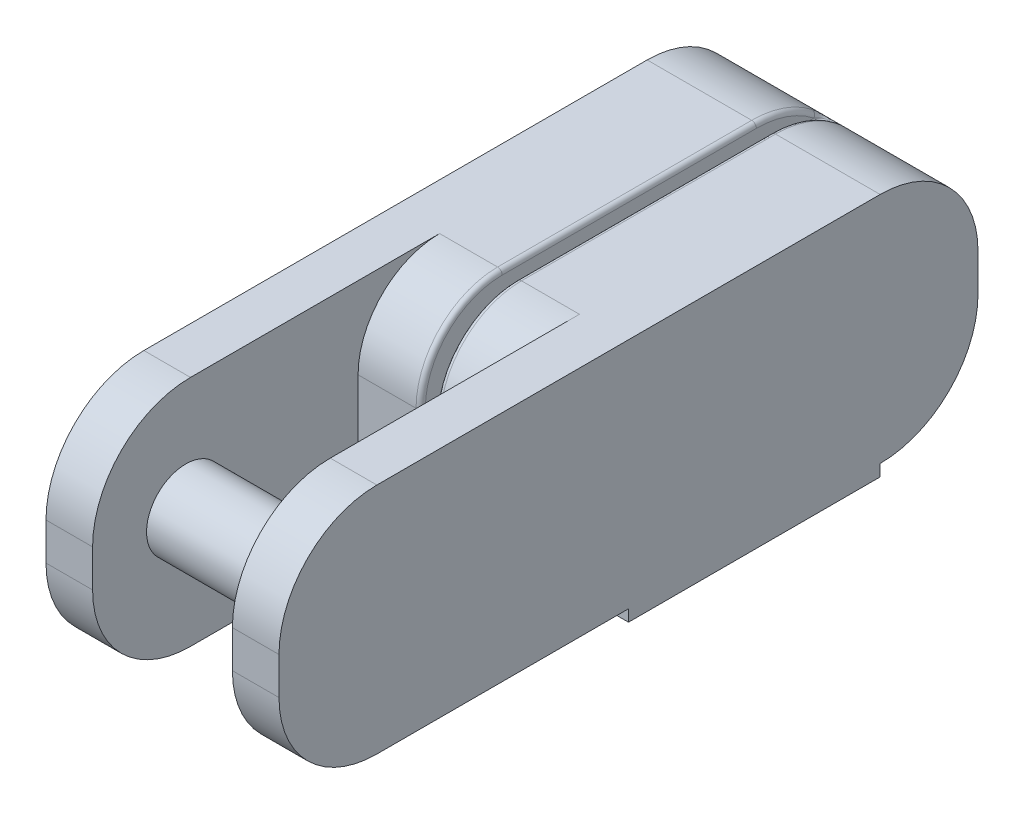
SolidWorks part; units mm, degrees
ref_plane "Front Plane" through (0, 0, 0) normal (0, 0, 1) x (1, 0, 0)
ref_plane "Top Plane" through (0, 0, 0) normal (0, 1, 0) x (1, 0, 0)
ref_plane "Right Plane" through (0, 0, 0) normal (1, 0, 0) x (0, 0, -1)
sketch "Sketch2" plane through (0, 0, 0) normal (0, 1, 0) x (1, 0, 0)
  line L0 (-31.2782, 19.6442) -> (-18.5782, 19.6442)
  line L2 (-31.2782, 19.6442) -> (-31.2782, -18.4558)
  line L3 (-31.2782, -18.4558) -> (-28.7382, -18.4558)
  line L4 (-18.5782, 19.6442) -> (-18.5782, -18.4558)
  line L7 (-28.7382, -18.4558) -> (-28.7382, -3.9858)
  line L8 (-28.7382, -3.9858) -> (-21.1182, -3.9858)
  line L9 (-21.1182, -3.9858) -> (-21.1182, -18.4558)
  line L10 (-31.2782, -3.9858) -> (-18.5782, -3.9858)
  line L11 (-21.1182, -18.4558) -> (-18.5782, -18.4558)
  point P3 (-30.0082, -18.4558)
  dimension "D1" = 38.1
  dimension "D2" = 12.7
  dimension "D3" = 2.54
  dimension "D4" = 2.54
  dimension "D8" = 14.47
extrude "Boss-Extrude1" add sketch "Sketch2" along normal blind 12.7 contours L2 L10 L8 L4 L0 | L0 | L9 L11 L4 L10 | L10 L2 L3 L7 region at (-24.9282, 0, -7.8292) region at (-30.0082, 0, 11.2208) region at (-19.8482, 0, 11.2208)
sketch "Sketch3" plane through (0, 0, 0) normal (1, 0, 0) x (0, 0, -1)
  line L0 (-13.3758, 12.7) -> (-13.3758, 0) construction
  line L1 (19.6442, 12.7) -> (-18.4558, 12.7) construction
  line L2 (19.6442, 0) -> (-18.4558, 0) construction
  line L3 (-18.4558, 12.7) -> (-18.4558, 0) construction
  line L4 (-18.4558, 6.6407) -> (19.6442, 6.35) construction
  line L6 (19.6442, 12.7) -> (19.6442, 0) construction
  circle A2 centre (-13.3758, 6.6019) radius 2.14
  dimension "D1" = 5.08
extrude "Cut-Extrude3" cut sketch "Sketch3" against normal through all
extrude "Boss-Extrude2" add sketch "Sketch3<2>" against normal through all from surface starting at face at (-18.5782, 6.6019, 11.2358)
sketch "Sketch3<2>" plane through (0, 0, 0) normal (1, 0, 0) x (0, 0, -1) same geometry as "Sketch3"
sketch "Sketch5" plane through (0, 0, 0) normal (0, 0, 1) x (1, 0, 0)
  line L0 (-24.9282, 12.7) -> (-24.9282, 0) construction
  line L1 (-28.7382, 12.7) -> (-21.1182, 12.7) construction
  line L2 (-28.7382, 0) -> (-21.1182, 0) construction
  line L4 (-25.3251, 12.7) -> (-24.5313, 12.7)
  line L5 (-25.3251, 12.7) -> (-25.3251, 0)
  line L6 (-25.3251, 0) -> (-24.5313, 0)
  line L7 (-24.5313, 12.7) -> (-24.5313, 0)
  dimension "D1" = 0.3969
  dimension "D2" = 0.3969
extrude "Cut-Extrude6" cut sketch "Sketch5" against normal blind 1.5875 from surface starting at face at (-24.9282, 6.35, 3.9858)
sketch "Sketch7" plane through (0, 12.7, 0) normal (0, 1, 0) x (1, 0, 0)
  line L0 (-24.9282, 19.6442) -> (-24.9282, -2.3983) construction
  line L1 (-31.2782, 19.6442) -> (-18.5782, 19.6442) construction
  line L2 (-24.5313, -2.3983) -> (-25.3251, -2.3983) construction
  line L4 (-25.3251, -2.3983) -> (-24.5313, -2.3983)
  line L5 (-25.3251, -2.3983) -> (-25.3251, 19.6442)
  line L6 (-25.3251, 19.6442) -> (-24.5313, 19.6442)
  line L7 (-24.5313, -2.3983) -> (-24.5313, 19.6442)
  dimension "D1" = 0.3969
extrude "Cut-Extrude7" cut sketch "Sketch7" against normal blind 1.5875 from surface starting at face at (-24.9282, 12.7, 4.6062)
sketch "Sketch8" plane through (0, 0, 0) normal (0, -1, 0) x (1, 0, 0)
  line L0 (-24.9282, 2.3983) -> (-24.9282, -19.6442) construction
  line L1 (-25.3251, 2.3983) -> (-24.5313, 2.3983) construction
  line L2 (-31.2782, -19.6442) -> (-18.5782, -19.6442) construction
  line L4 (-25.3251, 2.3983) -> (-24.5313, 2.3983)
  line L5 (-25.3251, 2.3983) -> (-25.3251, -19.6442)
  line L6 (-25.3251, -19.6442) -> (-24.5313, -19.6442)
  line L7 (-24.5313, 2.3983) -> (-24.5313, -19.6442)
  dimension "D1" = 0.3969
extrude "Cut-Extrude8" cut sketch "Sketch8" against normal blind 1.5875 from surface starting at face at (-24.9282, 0, 4.6062)
fillet "Fillet3" radius 5.334 8 edges at (-30.0082, 12.7, 18.4558) (-30.0082, 0, 18.4558) (-19.8482, 0, 18.4558) (-19.8482, 12.7, 18.4558) (-21.5547, 0, -19.6442) (-21.5547, 12.7, -19.6442) (-24.9282, 1.5875, 2.3983) (-24.9282, 11.1125, 2.3983)
fillet "Fillet4" radius 4.445 2 edges at (-22.8247, 0, 3.9858) (-22.8247, 12.7, 3.9858)
fillet "Fillet6" radius 0.254 24 edges at (-24.9282, 11.1125, -18.1069) (-24.9282, 1.5875, -18.1069) (-24.5313, 0.4129, -16.3678) (-24.5313, 1.5875, -10.5213) (-24.5313, 2.9529, 0.6282) (-24.5313, 9.7471, 0.6282) (-24.5313, 11.1125, -10.5213) (-24.5313, 12.2871, -16.3678) (-24.5313, 12.7, -7.3847) (-24.5313, 11.3981, 2.6839) (-24.5313, 6.35, 3.9858) (-24.5313, 1.3019, 2.6839) (-24.5313, 0, -7.3847) (-25.3251, 11.3981, 2.6839) (-25.3251, 12.7, -7.3847) (-25.3251, 12.2871, -16.3678) (-25.3251, 11.1125, -10.5213) (-25.3251, 9.7471, 0.6282) (-25.3251, 2.9529, 0.6282) (-25.3251, 1.5875, -10.5213) (-25.3251, 0.4129, -16.3678) (-25.3251, 0, -7.3847) (-25.3251, 1.3019, 2.6839) (-25.3251, 6.35, 3.9858)
sketch "Sketch12" plane through (0, 0, 0) normal (0, -1, 0) x (1, 0, 0)
  line L0 (-28.7382, -0.4592) -> (49971.2618, -0.4592) construction
  line L1 (-28.7382, 13.1218) -> (-28.7382, -49986.8782) construction
  line L2 (-31.2782, -14.3102) -> (-31.2782, 13.1218) construction
  line L3 (-31.2782, -0.5942) -> (-18.5782, -0.5942)
  line L4 (-31.2782, -0.5942) -> (-31.2782, -14.3102)
  line L5 (-31.2782, -14.3102) -> (-18.5782, -14.3102)
  line L6 (-18.5782, -0.5942) -> (-18.5782, -14.3102)
extrude "Boss-Extrude6" add sketch "Sketch12" along normal blind 0.635
